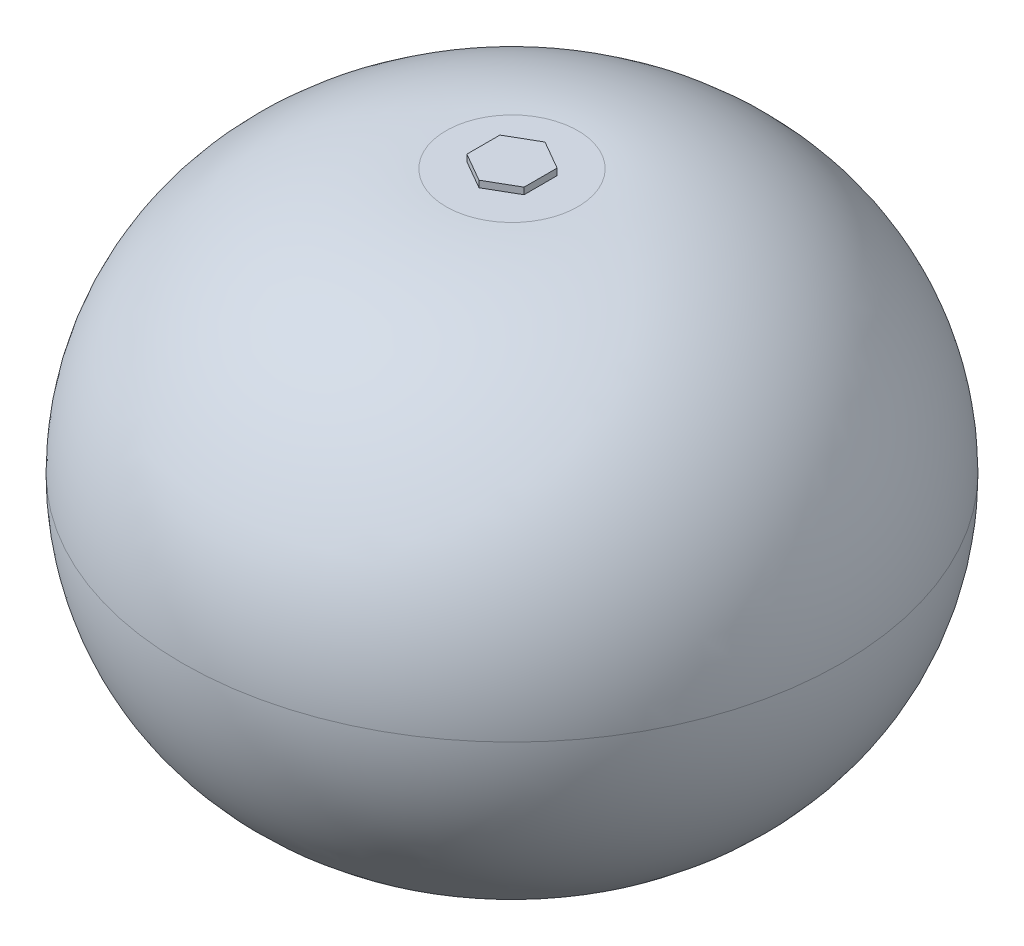
SolidWorks part; units mm, degrees
ref_plane "Front Plane" through (0, 0, 0) normal (0, 0, 1) x (1, 0, 0)
ref_plane "Top Plane" through (0, 0, 0) normal (0, 1, 0) x (1, 0, 0)
ref_plane "Right Plane" through (0, 0, 0) normal (1, 0, 0) x (0, 0, -1)
sketch "Sketch2" plane through (0, 0, 0) normal (0, 1, 0) x (1, 0, 0)
  line L5 (36.1989, -14.7713) -> (-36.1989, 14.7713) construction
  line L6 (36.1989, 14.7713) -> (-36.1989, -14.7713) construction
  circle A0 centre (0, 0) radius 25
  point P0 (0, 0)
  dimension "D1" = 50
extrude "Boss-Extrude5" add sketch "Sketch2" along normal mid plane 40 contours A0
fillet "Fillet8" radius 20 2 edges at (0, -20, 25) (0, 20, 25)
sketch "Sketch3" plane through (0, 20, 0) normal (0, 1, 0) x (1, 0, 0)
  line L1 (0, 2.5048) -> (-2.1692, 1.2524)
  line L2 (-2.1692, 1.2524) -> (-2.1692, -1.2524)
  line L3 (-2.1692, -1.2524) -> (0, -2.5048)
  line L4 (0, -2.5048) -> (2.1692, -1.2524)
  line L5 (2.1692, -1.2524) -> (2.1692, 1.2524)
  line L6 (2.1692, 1.2524) -> (0, 2.5048)
  circle A0 centre (0, 0) radius 2.1692 construction
extrude "Boss-Extrude6" add sketch "Sketch3" along normal blind 0.5
